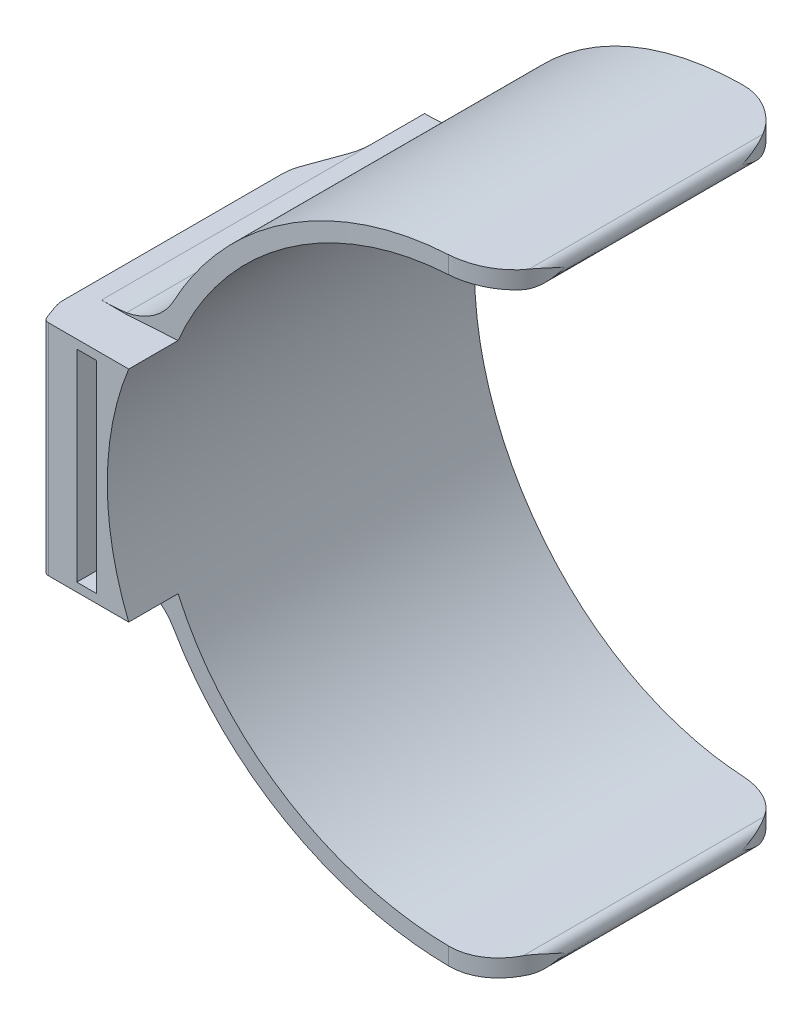
SolidWorks part; units mm, degrees
ref_plane "前视基准面" through (0, 0, 0) normal (0, 0, 1) x (1, 0, 0)
ref_plane "上视基准面" through (0, 0, 0) normal (0, 1, 0) x (1, 0, 0)
ref_plane "右视基准面" through (0, 0, 0) normal (1, 0, 0) x (0, 0, -1)
sketch "Sketch3" plane through (0, 0, 0) normal (0, 0, 1) x (1, 0, 0)
  line L1 (-4.5, 19) -> (4.5, 19)
  line L2 (-4.5, 19) -> (-4.5, -19)
  line L3 (-4.5, -19) -> (4.5, -19)
  line L4 (4.5, 19) -> (4.5, -19)
  line L5 (-4.5, 19) -> (4.5, -19) construction
  line L6 (-4.5, -19) -> (4.5, 19) construction
  point P0 (0, 0)
  dimension "D1" = 38
  dimension "D2" = 9
extrude "Boss-Extrude1" add sketch "Sketch3" along normal mid plane 56
sketch "Sketch4" plane through (0, 0, 0) normal (0, 0, 1) x (1, 0, 0)
  line L0 (-24.0082, 0) -> (58.1501, 0) construction
  line L1 (61.5, 50) -> (61.5, -50) construction
  line L2 (4.5, -19) -> (4.5, 19) construction
  line L3 (-4.5, 19) -> (-4.5, -19) construction
  line L5 (-4.5, -19) -> (4.5, -19) construction
  line L6 (4.5, 19) -> (-4.5, 19) construction
  line L7 (4.5, -19) -> (4.5, 19)
  line L8 (-4.5, -19) -> (4.5, -19)
  line L9 (-4.5, 19) -> (-4.5, -19)
  line L10 (4.5, 19) -> (-4.5, 19)
  arc A4 (61.5, 50) -> (61.5, -50) centre (54.9298, 0) ccw
  arc A10 (61.8909, 52.9744) -> (7.4936, 24.5876) centre (54.9298, 0) ccw
  arc A11 (61.5, 50) -> (61.8909, 52.9744) centre (61.6954, 51.4872) ccw
  arc A12 (61.5, -50) -> (61.8909, -52.9744) centre (61.6954, -51.4872) cw
  arc A13 (-4.5, 19) -> (-0.1726, 19.2632) centre (-4.5, 54.7041) ccw
  arc A14 (7.4936, -24.5876) -> (61.8909, -52.9744) centre (54.9298, 0) ccw
  arc A15 (61.8909, 52.9744) -> (61.8909, -52.9744) centre (54.9298, 0) ccw construction
  arc A16 (-0.1726, 19.2632) -> (7.4936, 24.5876) centre (-1.3846, 29.1895) ccw
  arc A17 (-4.5, -19) -> (-0.1726, -19.2632) centre (-4.5, -54.7041) cw
  arc A18 (-0.1726, -19.2632) -> (7.4936, -24.5876) centre (-1.3846, -29.1895) cw
  point P5 (61.5, 0)
  dimension "D4" = 10
  dimension "D1" = 57
  dimension "D2" = 100
  dimension "D3" = 3
extrude "Boss-Extrude3" add sketch "Sketch4" along normal mid plane 56 contours A16 A13 L10 L7 A4 A11 A10 | L7 L10 L9 L8 | A17 A18 A14 A12 A4 L7 L8 region at (0, 0, 0) region at (5.3624, -9.5, 0) region at (5.3624, 9.5, 0)
ref_plane "Plane1" through (0, 55, 0) normal (0, 1, 0) x (1, 0, 0)
sketch "Sketch5" plane through (0, 55, 0) normal (0, 1, 0) x (1, 0, 0)
  line L0 (-43.0641, 0) -> (87.3921, 0) construction
  line L1 (63.1954, 15) -> (63.1954, -15) construction
  line L2 (63.1954, -28) -> (63.1954, 28) construction
  line L3 (53.1954, 25.5) -> (53.1954, -25.5) construction
  line L4 (-0.1726, 28) -> (63.1954, 28)
  line L5 (63.1954, 28) -> (63.1954, 15)
  line L6 (-0.1726, -28) -> (63.1954, -28)
  line L7 (63.1954, -28) -> (63.1954, -15)
  arc A0 (53.1954, 25.5) -> (63.1954, 15) centre (52.9609, 15.2647) cw
  arc A1 (63.1954, -15) -> (53.1954, -25.5) centre (52.9454, -15.25) cw
  arc A2 (53.1954, 25.5) -> (-0.1726, 28) centre (78.8044, 1143.0601) cw
  arc A3 (53.1954, -25.5) -> (-0.1726, -28) centre (78.8044, -1143.0601) ccw
  point P7 (63.1954, 0)
  point P10 (22.164, 0)
  point P11 (53.1954, 0)
  dimension "D1" = 30
  dimension "D2" = 51
  dimension "D3" = 10
extrude "Cut-Extrude1" cut sketch "Sketch5" against normal up to next contours A2 A0 L5 L4 | A1 A3 L6 L7 region at (43.6975, 55, -26.3285) region at (43.7061, 55, 26.3262)
ref_plane "Plane2" through (0, 0, 36) normal (0, 0, 1) x (1, 0, 0)
sketch "Sketch6" plane through (0, 0, 36) normal (0, 0, 1) x (1, 0, 0)
  line L0 (-4.5, 19) -> (8.2162, 19)
  line L1 (-4.5, -19) -> (8.2162, -19)
  line L2 (-4.5, 19) -> (-7.7838, 19)
  line L3 (-7.7838, 19) -> (-7.7838, -19)
  line L4 (-7.7838, -19) -> (-4.5, -19)
  arc A0 (53.1954, 50.4) -> (53.1954, -50.4) centre (54.9298, 0) ccw construction
  arc A1 (8.2162, 19) -> (8.2162, -19) centre (54.9298, 0) ccw
  dimension "D1" = 16
extrude "Boss-Extrude4" add sketch "Sketch6" against normal blind 53
sketch "Sketch7" plane through (0, -19, 0) normal (0, -1, 0) x (1, 0, 0)
  line L0 (-4.8015, -16.1715) -> (-4.5, -17)
  line L2 (-4.8015, -16.1715) -> (-7.3014, -9.3032)
  line L3 (-7.7838, -17) -> (-7.7838, 36) construction
  line L4 (-4.5, -17) -> (-7.7838, -17)
  line L5 (-7.7838, -17) -> (-7.7838, -6.5671)
  line L6 (-7.4823, 33.0391) -> (-6.4046, 36)
  line L7 (-7.7838, 36) -> (8.2162, 36) construction
  line L8 (-7.7838, 31.329) -> (-7.7838, 36)
  line L9 (-7.7838, 36) -> (-6.4046, 36)
  arc A0 (-7.4823, 33.0391) -> (-7.7838, 31.329) centre (-2.7838, 31.329) ccw
  arc A1 (-7.3014, -9.3032) -> (-7.7838, -6.5671) centre (0.2162, -6.5671) cw
  point P11 (-4.5, -17)
  point P14 (-7.7838, -7.9777)
  point P19 (-7.7838, 32.2106)
  dimension "D1" = 5
  dimension "D2" = 8
extrude "Cut-Extrude2" cut sketch "Sketch7" against normal up to next
fillet "Fillet1" radius 10 1 edges at (-4.5, 0, -17)
fillet "Fillet2" radius 1 1 edges at (-6.4046, 0, 36)
sketch "Sketch8" plane through (0, 0, 36) normal (0, 0, 1) x (1, 0, 0)
  line L0 (-7.7838, 19) -> (-7.7838, -19) construction
  line L1 (2.6162, -17.5) -> (-0.7838, -17.5)
  line L2 (2.6162, -17.5) -> (2.6162, 17.5)
  line L3 (2.6162, 17.5) -> (-0.7838, 17.5)
  line L4 (-0.7838, -17.5) -> (-0.7838, 17.5)
  line L5 (2.6162, -17.5) -> (-0.7838, 17.5) construction
  line L6 (2.6162, 17.5) -> (-0.7838, -17.5) construction
  point P0 (0.9162, 0)
  dimension "D1" = 7
  dimension "D2" = 3.4
  dimension "D3" = 35
extrude "Cut-Extrude3" cut sketch "Sketch8" against normal blind 35
